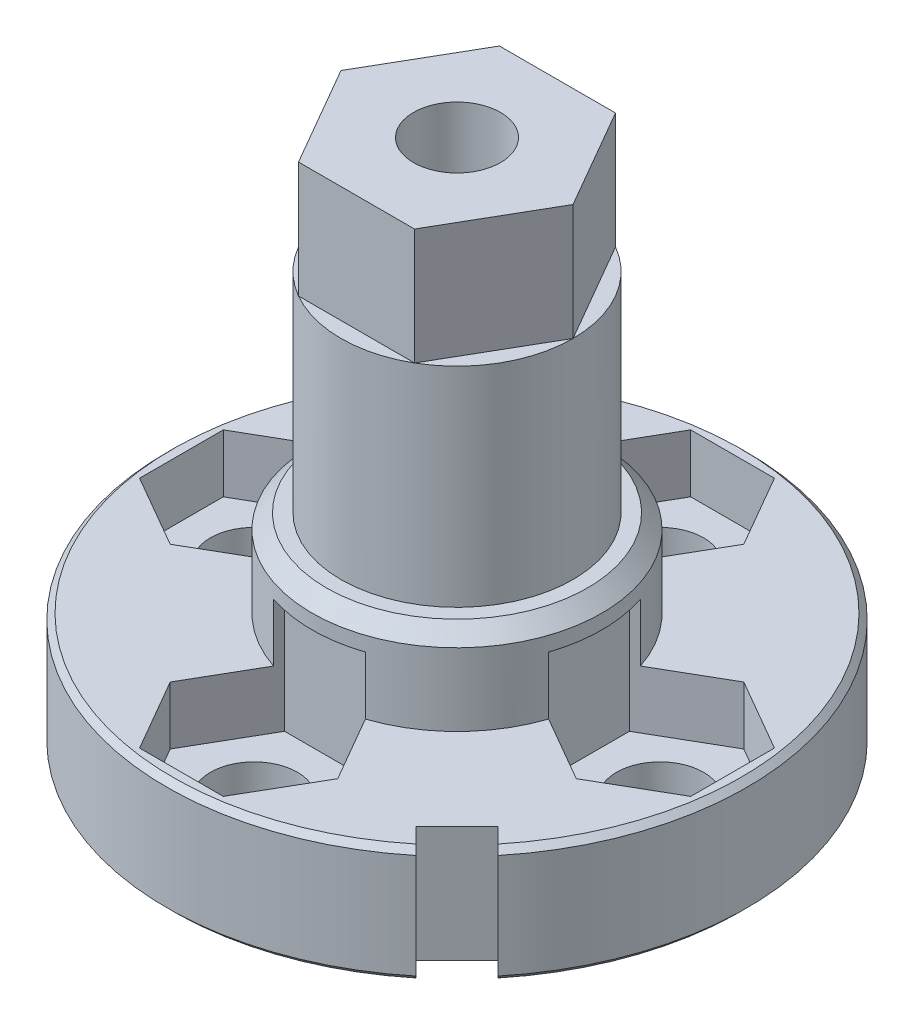
SolidWorks part; units mm, degrees
ref_plane "Front Plane" through (0, 0, 0) normal (0, 0, 1) x (1, 0, 0)
ref_plane "Top Plane" through (0, 0, 0) normal (0, 1, 0) x (1, 0, 0)
ref_plane "Right Plane" through (0, 0, 0) normal (1, 0, 0) x (0, 0, -1)
sketch "Sketch1" plane through (0, 0, 0) normal (0, 1, 0) x (1, 0, 0)
  circle A0 centre (0, 0) radius 4
  dimension "D1" = 8
extrude "Boss-Extrude1" add sketch "Sketch1" along normal blind 7.2
sketch "Sketch2" plane through (0, 7.2, 0) normal (0, 1, 0) x (1, 0, 0)
  line L1 (2, 3.4641) -> (-2, 3.4641)
  line L2 (-2, 3.4641) -> (-4, 0)
  line L3 (-4, 0) -> (-2, -3.4641)
  line L4 (-2, -3.4641) -> (2, -3.4641)
  line L5 (2, -3.4641) -> (4, 0)
  line L6 (4, 0) -> (2, 3.4641)
  circle A0 centre (0, 0) radius 3.4641 construction
  circle A1 centre (0, 0) radius 4
  dimension "D1" = 8
extrude "Boss-Extrude2" add sketch "Sketch2" along normal blind 4 contours L5 L6 L1 L2 L3 L4 region at (0, 7.2, 0)
sketch "Sketch3" plane through (0, 0, 0) normal (0, -1, 0) x (1, 0, 0)
  circle A0 centre (0, 0) radius 5
  dimension "D1" = 10
extrude "Boss-Extrude3" add sketch "Sketch3" along normal blind 3
chamfer "Chamfer1" distance 0.5 angle 45 1 edges at (0, 0, -5)
sketch "Sketch4" plane through (0, -3, 0) normal (0, -1, 0) x (1, 0, 0)
  circle A0 centre (0, 0) radius 10
  dimension "D1" = 20
extrude "Boss-Extrude4" add sketch "Sketch4" along normal blind 4
chamfer "Chamfer2" distance 0.2 angle 45 2 edges at (0, -7, -10) (0, -3, -10)
sketch "Sketch5" plane through (0, -7, 0) normal (0, -1, 0) x (1, 0, 0)
  circle A0 centre (0, 0) radius 1.5
  dimension "D1" = 3
extrude "Cut-Extrude1" cut sketch "Sketch5" against normal through all
sketch "Sketch6" plane through (0, -7, 0) normal (0, -1, 0) x (1, 0, 0)
  line L1 (2, 3.4641) -> (-2, 3.4641)
  line L2 (-2, 3.4641) -> (-4, 0)
  line L3 (-4, 0) -> (-2, -3.4641)
  line L4 (-2, -3.4641) -> (2, -3.4641)
  line L5 (2, -3.4641) -> (4, 0)
  line L6 (4, 0) -> (2, 3.4641)
  circle A0 centre (0, 0) radius 3.4641 construction
  circle A1 centre (0, 0) radius 4
  circle M3 centre (0, 0) radius 1.5
  dimension "D1" = 8
extrude "Cut-Extrude2" cut sketch "Sketch6" against normal blind 4 contours L5 L6 L1 L2 L3 L4 M3 region at (2.9083, -7, 1.6791)
sketch "Sketch7" plane through (0, -7, 0) normal (0, -1, 0) x (1, 0, 0)
  line L0 (1.4434, 4.5) -> (2.8868, 7)
  line L1 (-4.5, 1.4434) -> (-7, 2.8868)
  line L2 (-7, 2.8868) -> (-9.5, 1.4434)
  line L3 (-9.5, 1.4434) -> (-9.5, -1.4434)
  line L4 (-9.5, -1.4434) -> (-7, -2.8868)
  line L5 (-7, -2.8868) -> (-4.5, -1.4434)
  line L6 (-4.5, -1.4434) -> (-4.5, 1.4434)
  line L7 (2.8868, 7) -> (1.4434, 9.5)
  line L8 (1.4434, 9.5) -> (-1.4434, 9.5)
  line L9 (-1.4434, 9.5) -> (-2.8868, 7)
  line L10 (-2.8868, 7) -> (-1.4434, 4.5)
  line L11 (-1.4434, 4.5) -> (1.4434, 4.5)
  line L12 (4.5, -1.4434) -> (7, -2.8868)
  line L13 (7, -2.8868) -> (9.5, -1.4434)
  line L14 (9.5, -1.4434) -> (9.5, 1.4434)
  line L15 (9.5, 1.4434) -> (7, 2.8868)
  line L16 (7, 2.8868) -> (4.5, 1.4434)
  line L17 (4.5, 1.4434) -> (4.5, -1.4434)
  line L18 (-1.4434, -4.5) -> (-2.8868, -7)
  line L19 (-2.8868, -7) -> (-1.4434, -9.5)
  line L20 (-1.4434, -9.5) -> (1.4434, -9.5)
  line L21 (1.4434, -9.5) -> (2.8868, -7)
  line L22 (2.8868, -7) -> (1.4434, -4.5)
  line L23 (1.4434, -4.5) -> (-1.4434, -4.5)
  circle A0 centre (-7, 0) radius 1.5
  circle A1 centre (0, 7) radius 1.5
  circle A2 centre (7, 0) radius 1.5
  circle A3 centre (0, -7) radius 1.5
  circle A4 centre (0, 0) radius 7 construction
  circle A5 centre (-7, 0) radius 2.5 construction
  point P39 (0, 0)
  dimension "D1" = 14
  dimension "D2" = 3
  dimension "D3" = 3
  dimension "D4" = 5
  dimension "D6" = 0.5
  dimension "D7" = 1.1132
  dimension "D5" = 4
extrude "Cut-Extrude3" cut sketch "Sketch7" against normal blind 4 contours A0 | A3 | A2 | A1 region at (-7, -7, 0) region at (0, -7, 7) region at (7, -7, 0) region at (0, -7, -7)
extrude "Cut-Extrude4" cut sketch "Sketch7<3>" against normal blind 4 from offset 2 offset against normal yes
sketch "Sketch7<3>" plane through (0, -7, 0) normal (0, -1, 0) x (1, 0, 0) same geometry as "Sketch7"
sketch "Sketch8" plane through (0, -3, 0) normal (0, -1, 0) x (1, 0, 0)
  line L1 (1.5877, 2.75) -> (-1.5877, 2.75)
  line L2 (-1.5877, 2.75) -> (-3.1754, 0)
  line L3 (-3.1754, 0) -> (-1.5877, -2.75)
  line L4 (-1.5877, -2.75) -> (1.5877, -2.75)
  line L5 (1.5877, -2.75) -> (3.1754, 0)
  line L6 (3.1754, 0) -> (1.5877, 2.75)
  circle A0 centre (0, 0) radius 2.75 construction
  dimension "D1" = 5.5
extrude "Cut-Extrude5" cut sketch "Sketch8" against normal blind 5
sketch "Sketch9" plane through (0, -7, 0) normal (0, -1, 0) x (1, 0, 0)
  line L0 (8.4853, 9.8995) -> (5.6569, 7.0711)
  line L1 (5.6569, 7.0711) -> (7.0711, 5.6569)
  line L2 (7.0711, 5.6569) -> (9.8995, 8.4853)
  line L3 (9.8995, 8.4853) -> (8.4853, 9.8995)
  line L4 (0, 0) -> (0, 9.8) construction
  line L5 (0, 0) -> (6.9296, 6.9296) construction
  circle A0 centre (0, 0) radius 9.8 construction
  point P10 (6.364, 6.364)
  dimension "D3" = 4
  dimension "D1" = 45
  dimension "D2" = 2
  dimension "D4" = 9
extrude "Cut-Extrude6" cut sketch "Sketch9" against normal blind 10
